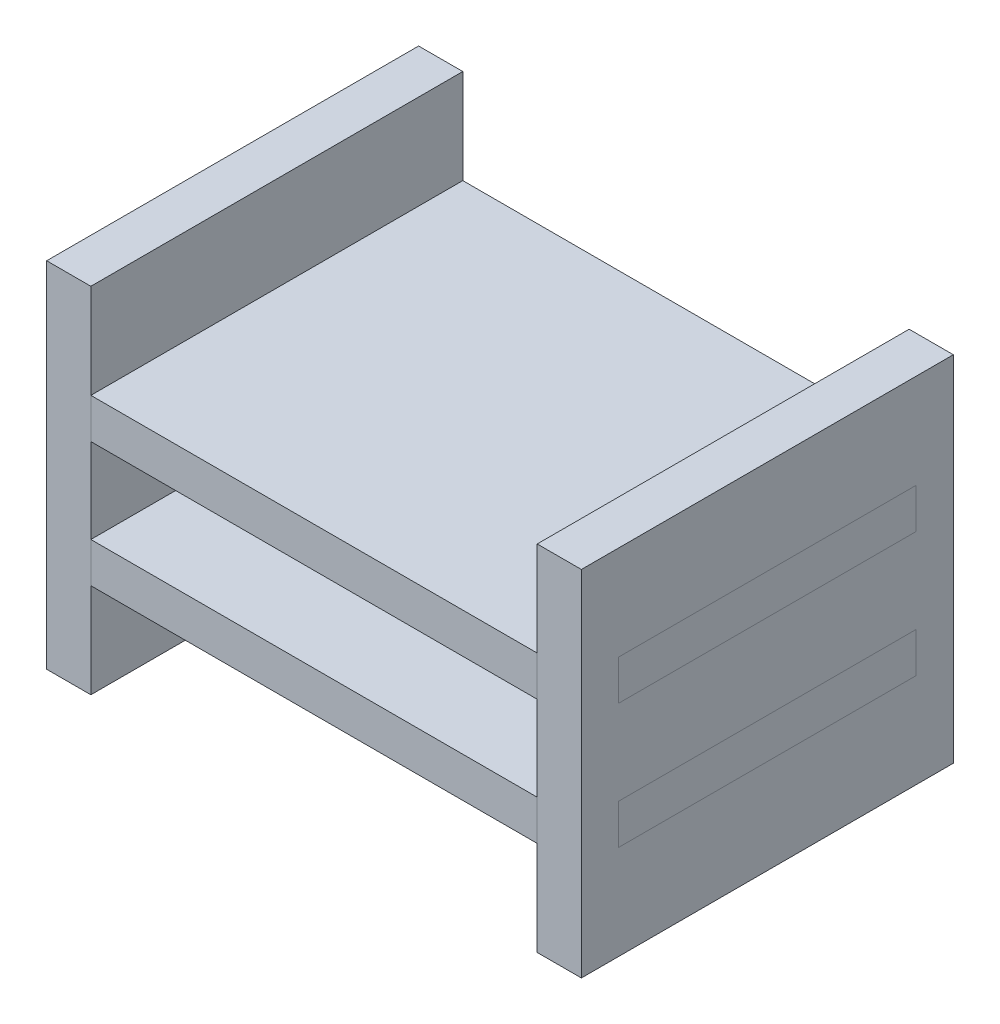
SolidWorks part; units mm, degrees
ref_plane "Front" through (0, 0, 0) normal (0, 0, 1) x (1, 0, 0)
ref_plane "Top" through (0, 0, 0) normal (0, 1, 0) x (1, 0, 0)
ref_plane "Right" through (0, 0, 0) normal (1, 0, 0) x (0, 0, -1)
sketch "Sketch2" plane through (0, 0, 0) normal (0, 1, 0) x (1, 0, 0)
  line L1 (-15, 12.5) -> (15, 12.5)
  line L2 (-15, 12.5) -> (-15, -12.5)
  line L3 (-15, -12.5) -> (15, -12.5)
  line L4 (15, 12.5) -> (15, -12.5)
  line L5 (-15, 12.5) -> (15, -12.5) construction
  line L6 (-15, -12.5) -> (15, 12.5) construction
  line L7 (-15, 10) -> (-17.97, 10)
  line L8 (-15, 10) -> (-15, -10)
  line L9 (-15, -10) -> (-17.97, -10)
  line L10 (-17.97, 10) -> (-17.97, -10)
  line L11 (-15, 10) -> (-17.97, -10) construction
  line L12 (-15, -10) -> (-17.97, 10) construction
  line L13 (15, 10) -> (17.97, 10)
  line L14 (15, 10) -> (15, -10)
  line L15 (15, -10) -> (17.97, -10)
  line L16 (17.97, 10) -> (17.97, -10)
  line L17 (15, 10) -> (17.97, -10) construction
  line L18 (15, -10) -> (17.97, 10) construction
  point P4 (0, 0)
  point P11 (-16.485, 0)
  point P16 (16.485, 0)
  dimension "D1" = 2.97
  dimension "D2" = 30
  dimension "D3" = 25
  dimension "D4" = 20
extrude "Boss-Extrude3" add sketch "Sketch2" along normal blind 2.69 contours L4 L1 L2 L3 | L7 L10 L9 L2 | L16 L13 L4 L15 region at (0, 0, 0) region at (-16.485, 0, 0) region at (16.485, 0, 0)
extrude "Boss-Extrude4" add sketch "Sketch2<3>" along normal blind 2.69 from offset 8.39 separate body contours L7 L10 L9 L2 | L4 L1 L2 L3 | L16 L13 L4 L15 region at (0, 0, 0) region at (-16.485, 0, 0) region at (16.485, 0, 0)
sketch "Sketch2<3>" plane through (0, 0, 0) normal (0, 1, 0) x (1, 0, 0) same geometry as "Sketch2"
sketch "Sketch4" plane through (15, 0, 0) normal (1, 0, 0) x (0, 0, -1)
  line L0 (0, 50) -> (0, -50) construction
  line L1 (12.5, -6.35) -> (-12.5, -6.35)
  line L2 (12.5, -6.35) -> (12.5, 17.43)
  line L3 (12.5, 17.43) -> (-12.5, 17.43)
  line L4 (-12.5, -6.35) -> (-12.5, 17.43)
  line L5 (12.5, -6.35) -> (-12.5, 17.43) construction
  line L6 (12.5, 17.43) -> (-12.5, -6.35) construction
  line L7 (-12.5, 11.08) -> (-12.5, 8.39) construction
  line L8 (-10, 11.08) -> (-12.5, 11.08) construction
  line L9 (0, 8.39) -> (0, 2.69) construction
  line L10 (10, 8.39) -> (-10, 8.39) construction
  line L11 (10, 2.69) -> (-10, 2.69) construction
  line L12 (-10, 11.08) -> (-10, 8.39) construction
  line L13 (-10, 11.08) -> (10, 11.08)
  line L14 (-10, 11.08) -> (-10, 8.39)
  line L15 (-10, 8.39) -> (10, 8.39)
  line L16 (10, 11.08) -> (10, 8.39)
  line L17 (-10, 11.08) -> (10, 8.39) construction
  line L18 (-10, 8.39) -> (10, 11.08) construction
  line L19 (10, 11.08) -> (-10, 11.08) construction
  line L21 (10, 2.69) -> (-10, 2.69)
  line L22 (10, 2.69) -> (10, 0)
  line L23 (10, 0) -> (-10, 0)
  line L24 (-10, 2.69) -> (-10, 0)
  line L25 (10, 2.69) -> (-10, 0) construction
  line L26 (10, 0) -> (-10, 2.69) construction
  point P0 (0, 5.54)
  point P19 (0, 5.54)
  point P22 (0, 9.735)
  point P32 (0, 1.345)
  dimension "D1" = 6.35
extrude "Boss-Extrude5" add sketch "Sketch4" along normal up to surface (2.97 mm away) separate body up to face at (17.97, 9.735, 0)
mirror "Mirror1" about plane through (0, 0, 0) normal (1, 0, 0) of bodies 105
